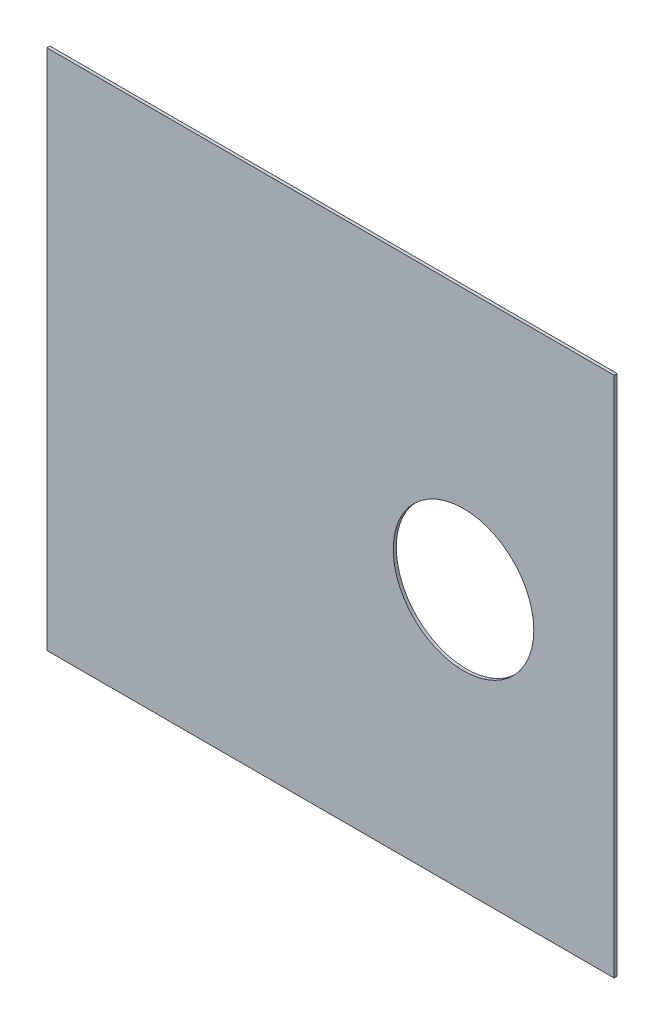
SolidWorks part; units mm, degrees
ref_plane "Přední rovina" through (0, 0, 0) normal (0, 0, 1) x (1, 0, 0)
ref_plane "Horní rovina" through (0, 0, 0) normal (0, 1, 0) x (1, 0, 0)
ref_plane "Pravá rovina" through (0, 0, 0) normal (1, 0, 0) x (0, 0, -1)
sketch "Skica1" plane through (0, 0, 0) normal (0, 0, 1) x (1, 0, 0)
  line L1 (-282.5, 260) -> (282.5, 260)
  line L2 (-282.5, 260) -> (-282.5, -260)
  line L3 (-282.5, -260) -> (282.5, -260)
  line L4 (282.5, 260) -> (282.5, -260)
  line L5 (-282.5, 260) -> (282.5, -260) construction
  line L6 (-282.5, -260) -> (282.5, 260) construction
  circle A0 centre (132.5, 0) radius 70
  point P0 (0, 0)
  dimension "D3" = 140
  dimension "D1" = 565
  dimension "D2" = 520
  dimension "D4" = 150
extrude "Přidat vysunutím1" add sketch "Skica1" along normal blind 3
